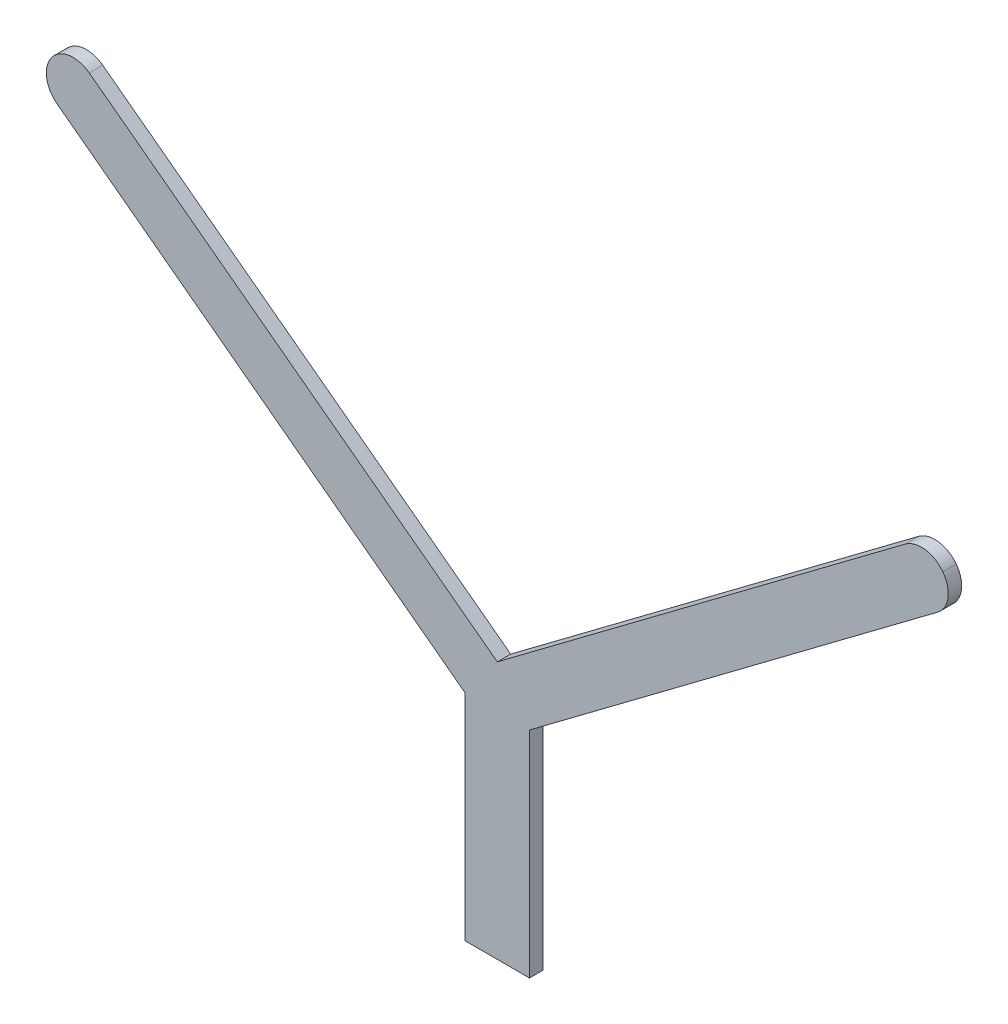
SolidWorks part; units mm, degrees
ref_plane "Front Plane" through (0, 0, 0) normal (0, 0, 1) x (1, 0, 0)
ref_plane "Top Plane" through (0, 0, 0) normal (0, 1, 0) x (1, 0, 0)
ref_plane "Right Plane" through (0, 0, 0) normal (1, 0, 0) x (0, 0, -1)
sketch "Sketch6" plane through (0, 0, 0) normal (0, 0, 1) x (1, 0, 0)
  line L0 (0, 0) -> (0, -573.9285) construction
  line L3 (-203.2, -355.3961) -> (0, -507.7975)
  line L4 (0, -507.7975) -> (203.2, -355.3961)
  line L5 (203.2, -355.3961) -> (218.4401, -375.7161)
  line L6 (218.4401, -375.7161) -> (15.2401, -528.1174)
  line L8 (-203.2, -355.3961) -> (-218.4401, -375.7161)
  line L9 (-218.4401, -375.7161) -> (-15.2401, -528.1174)
  line L12 (-15.2401, -528.1174) -> (-15.2401, -629.7174)
  line L13 (-15.2401, -629.7174) -> (15.2401, -629.7174)
  line L14 (15.2401, -629.7174) -> (15.2401, -528.1174)
  circle A0 centre (0, 0) radius 406.4 construction
  point P3 (0, 0)
  point P14 (0, -629.7174)
  dimension "D1" = 812.8
  dimension "D2" = 25.4
  dimension "D3" = 101.6
  dimension "D4" = 30.4802
  dimension "D5" = 406.4
  dimension "D6" = 25.4
  dimension "D7" = 254.0008
  dimension "D8" = 106.26
extrude "Boss-Extrude2" add sketch "Sketch6" along normal blind 6.35 contours L6 L14 L13 L12 L9 L8 L3 L4 L5
fillet "Fillet1" radius 12.7 1 edges at (203.2, -355.3961, 3.175)
fillet "Fillet2" radius 12.7 1 edges at (218.4401, -375.7161, 3.175)
fillet "Fillet3" radius 12.7 1 edges at (-203.2, -355.3961, 3.175)
fillet "Fillet4" radius 12.7 1 edges at (-218.4401, -375.7161, 3.175)
